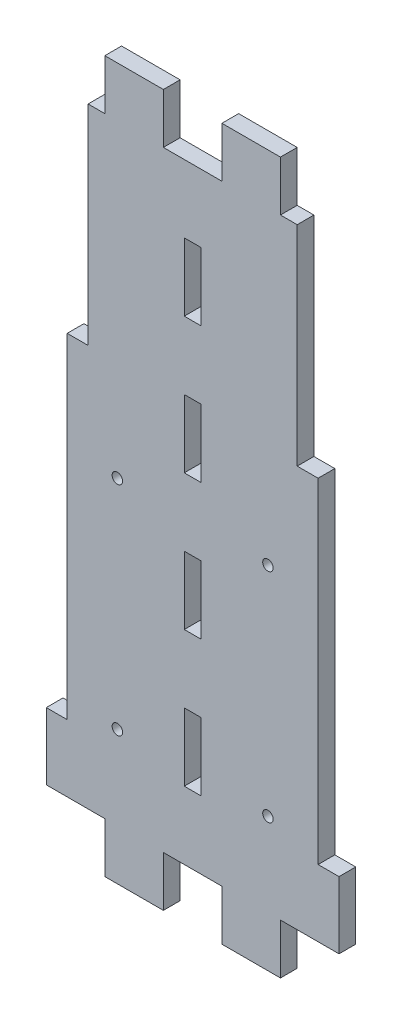
SolidWorks part; units mm, degrees
material "Beech"
ref_plane "Front Plane" through (0, 0, 0) normal (0, 0, 1) x (1, 0, 0)
ref_plane "Top Plane" through (0, 0, 0) normal (0, 1, 0) x (1, 0, 0)
ref_plane "Right Plane" through (0, 0, 0) normal (1, 0, 0) x (0, 0, -1)
sketch "Sketch1" plane through (0, 0, 0) normal (0, 0, 1) x (1, 0, 0)
  line L0 (0, 0) -> (17.78, 0)
  line L1 (17.78, 0) -> (17.78, 15.24)
  line L2 (17.78, 15.24) -> (35.56, 15.24)
  line L3 (35.56, 15.24) -> (35.56, 0)
  line L4 (35.56, 0) -> (53.34, 0)
  line L5 (53.34, 0) -> (53.34, 15.24)
  line L6 (53.34, 15.24) -> (71.12, 15.24)
  line L7 (71.12, 15.24) -> (71.12, 0)
  line L8 (71.12, 0) -> (88.9, 0)
  line L9 (88.9, 0) -> (88.9, -185.42)
  line L10 (0, 0) -> (0, -185.42)
  line L11 (88.9, -92.71) -> (0, -92.71) construction
  line L12 (0, -185.42) -> (17.78, -185.42)
  line L13 (71.12, -185.42) -> (88.9, -185.42)
  line L14 (71.12, -200.66) -> (71.12, -185.42)
  line L15 (53.34, -200.66) -> (71.12, -200.66)
  line L16 (53.34, -185.42) -> (53.34, -200.66)
  line L17 (35.56, -185.42) -> (53.34, -185.42)
  line L18 (35.56, -200.66) -> (35.56, -185.42)
  line L19 (17.78, -200.66) -> (35.56, -200.66)
  line L20 (17.78, -185.42) -> (17.78, -200.66)
  dimension "D1" = 185.42
  dimension "D2" = 88.9
  dimension "D3" = 15.24
extrude "Boss-Extrude1" add sketch "Sketch1" along normal blind 5.08
sketch "Sketch2" plane through (0, 0, 5.08) normal (0, 0, 1) x (1, 0, 0)
  line L0 (35.56, -185.42) -> (53.34, -185.42) construction
  line L1 (21.59, -160.02) -> (67.31, -160.02) construction
  line L2 (21.59, -160.02) -> (21.59, -93.98) construction
  line L3 (21.59, -93.98) -> (67.31, -93.98) construction
  line L4 (67.31, -160.02) -> (67.31, -93.98) construction
  line L5 (21.59, -160.02) -> (67.31, -93.98) construction
  line L6 (21.59, -93.98) -> (67.31, -160.02) construction
  line L7 (53.34, 0) -> (35.56, 0) construction
  circle A0 centre (21.59, -93.98) radius 1.5875
  circle A1 centre (67.31, -93.98) radius 1.5875
  circle A2 centre (67.31, -160.02) radius 1.5875
  circle A3 centre (21.59, -160.02) radius 1.5875
  point P0 (44.45, -127)
  point P10 (44.45, 0)
  dimension "D4" = 3.175
  dimension "D1" = 45.72
  dimension "D2" = 66.04
  dimension "D3" = 25.4
extrude "Cut-Extrude1" cut sketch "Sketch2" against normal through all
sketch "Sketch3" plane through (0, 0, 0) normal (0, 0, -1) x (-1, 0, 0)
  line L0 (-41.91, -20.6022) -> (-41.91, 0) construction
  line L1 (-46.99, -164.8178) -> (-41.91, -164.8178)
  line L2 (-46.99, -164.8178) -> (-46.99, -144.2156)
  line L3 (-46.99, -144.2156) -> (-41.91, -144.2156)
  line L4 (-41.91, -164.8178) -> (-41.91, -144.2156)
  line L5 (-46.99, -164.8178) -> (-41.91, -144.2156) construction
  line L6 (-46.99, -144.2156) -> (-41.91, -164.8178) construction
  line L7 (-46.99, -82.4089) -> (-41.91, -82.4089)
  line L8 (-46.99, -82.4089) -> (-46.99, -61.8067)
  line L9 (-46.99, -61.8067) -> (-41.91, -61.8067)
  line L10 (-41.91, -82.4089) -> (-41.91, -61.8067)
  line L11 (-46.99, -82.4089) -> (-41.91, -61.8067) construction
  line L12 (-46.99, -61.8067) -> (-41.91, -82.4089) construction
  line L13 (-46.99, -41.2044) -> (-41.91, -41.2044)
  line L14 (-46.99, -41.2044) -> (-46.99, -20.6022)
  line L15 (-46.99, -20.6022) -> (-41.91, -20.6022)
  line L16 (-41.91, -41.2044) -> (-41.91, -20.6022)
  line L17 (-46.99, -41.2044) -> (-41.91, -20.6022) construction
  line L18 (-46.99, -20.6022) -> (-41.91, -41.2044) construction
  line L19 (-46.99, -123.6133) -> (-41.91, -123.6133)
  line L20 (-46.99, -123.6133) -> (-46.99, -103.0111)
  line L21 (-46.99, -103.0111) -> (-41.91, -103.0111)
  line L22 (-41.91, -123.6133) -> (-41.91, -103.0111)
  line L23 (-46.99, -123.6133) -> (-41.91, -103.0111) construction
  line L24 (-46.99, -103.0111) -> (-41.91, -123.6133) construction
  line L25 (-53.34, 0) -> (-35.56, 0) construction
  line L27 (-41.91, -61.8067) -> (-41.91, -41.2044) construction
  line L28 (-41.91, -82.4089) -> (-41.91, -103.0111) construction
  line L29 (-41.91, -144.2156) -> (-41.91, -123.6133) construction
  line L30 (-41.91, -164.8178) -> (-41.91, -185.42) construction
  line L31 (-35.56, -185.42) -> (-53.34, -185.42) construction
  point P0 (-44.45, -154.5167)
  point P5 (-44.45, -72.1078)
  point P10 (-44.45, -30.9033)
  point P15 (-44.45, -113.3122)
  point P28 (-44.45, 0)
  dimension "D1" = 5.08
extrude "Cut-Extrude2" cut sketch "Sketch3" against normal through all
sketch "Sketch4" plane through (0, 0, 0) normal (0, 0, -1) x (-1, 0, 0)
  line L0 (-88.9, -185.42) -> (-88.9, 0) construction
  line L1 (-88.9, 0) -> (-76.2, 0)
  line L2 (-88.9, 0) -> (-88.9, -63.5)
  line L3 (-88.9, -63.5) -> (-76.2, -63.5) construction
  line L4 (-76.2, 0) -> (-76.2, -63.5)
  line L5 (-88.9, -165.1) -> (-82.55, -165.1)
  line L6 (-88.9, -165.1) -> (-88.9, -63.5)
  line L7 (-88.9, -63.5) -> (-82.55, -63.5) construction
  line L8 (-82.55, -165.1) -> (-82.55, -63.5)
  line L9 (-82.55, -63.5) -> (-76.2, -63.5)
  line L10 (-44.45, 0) -> (-44.45, -185.42) construction
  line L11 (-53.34, 0) -> (-35.56, 0) construction
  line L12 (-35.56, -185.42) -> (-53.34, -185.42) construction
  line L13 (0, -63.5) -> (-6.35, -63.5) construction
  line L14 (0, -63.5) -> (-12.7, -63.5) construction
  line L15 (-6.35, -63.5) -> (-12.7, -63.5)
  line L16 (-6.35, -165.1) -> (-6.35, -63.5)
  line L17 (0, -165.1) -> (0, -63.5)
  line L18 (0, -165.1) -> (-6.35, -165.1)
  line L19 (-12.7, 0) -> (-12.7, -63.5)
  line L20 (0, 0) -> (0, -63.5)
  line L21 (0, 0) -> (-12.7, 0)
  dimension "D1" = 63.5
  dimension "D2" = 101.6
  dimension "D3" = 12.7
extrude "Cut-Extrude3" cut sketch "Sketch4" against normal through all
